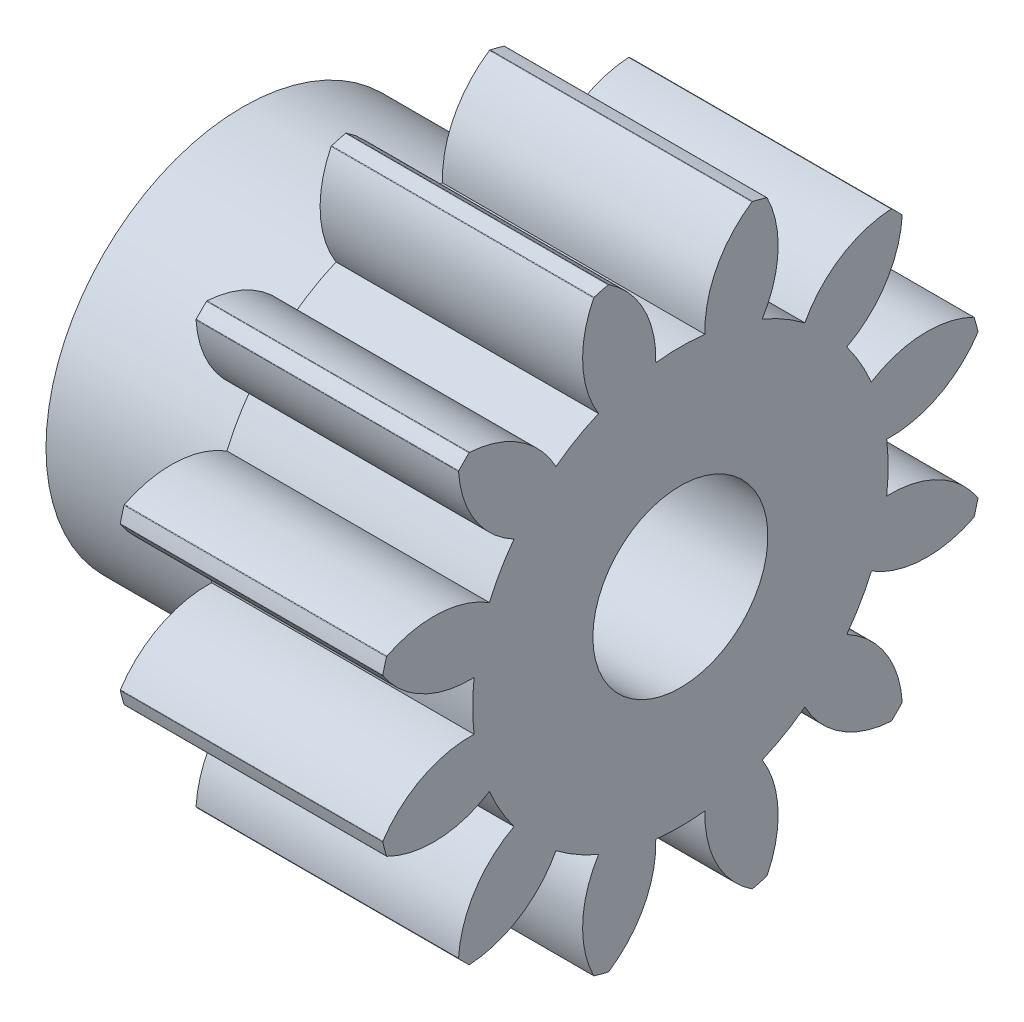
SolidWorks part; units mm, degrees
material "1.7035 (41Cr4)"
ref_plane "Plane1" through (0, 0, 0) normal (0, 0, 1) x (1, 0, 0)
ref_plane "Plane2" through (0, 0, 0) normal (0, 1, 0) x (1, 0, 0)
ref_plane "Plane3" through (0, 0, 0) normal (1, 0, 0) x (0, 0, -1)
sketch "HoldingSke" plane through (0, 0, 0) normal (0, 1, 0) x (1, 0, 0)
  line L0 (0, 0) -> (0.9781, -0.2079)
  line L1 (-15, 0) -> (100, 0) construction
  line L2 (0, 0) -> (-2.1039, 2.3779)
  line L3 (0, 0) -> (-11.863, 4.5341)
  line L4 (0, 0) -> (8.4473, 1.7955)
  line L5 (0, 0) -> (-46.8476, -17.4728)
  line L6 (0, 0) -> (-4.9738, -3.3558)
  line L7 (-2.1039, 2.3779) -> (8.6586, 51.2059)
  line L8 (-76.2, 54.61) -> (-75.5, 54.61)
  line L9 (-71.009, 38.7566) -> (-53.1078, 45.2721)
  line L10 (-76.2, 71.12) -> (104.1128, 71.12)
  line L11 (0, 0) -> (-6, 0)
  line L12 (-76.2, 101.6) -> (-76.162, 101.6)
  line L13 (24.9733, 27.94) -> (52.9518, 28.4284)
  line L14 (24.9733, 27.94) -> (24.9743, 27.94)
  line L15 (24.9733, 27.94) -> (100.4006, 29.5858)
  line L16 (-63.627, -1) -> (-12.827, -1)
  circle A0 centre (0, 0) radius 2
  circle A1 centre (0, 0) radius 4.749
  circle A2 centre (0, 0) radius 37.5
  circle A3 centre (0, 0) radius 2
  dimension "Num_teeth" = 12
  dimension "Pitch_radius" = 180.3128
  dimension "Width" = 6
  dimension "Thickness" = 6
sketch "BasProSke" plane through (0, 0, 0) normal (0, 1, 0) x (1, 0, 0)
  line L0 (-10, 0) -> (60, 0) construction
  line L1 (0, 0) -> (0, 7)
  line L2 (0, 0) -> (6, 0)
  line L3 (6, 0) -> (6, 7)
  line L4 (6, 7) -> (0, 7)
  dimension "Thickness" = 6
  dimension "Diameter" = 14
revolve "Base-Revolve" add sketch "BasProSke" angle 360 about L0
sketch "TooCutSke" plane through (0, 0, 0) normal (1, 0, 0) x (0, 0, -1)
  line L1 (0, 0) -> (0, 107) construction
  line L2 (0, 0) -> (-0.8496, 5.9395) construction
  line L3 (0, 0) -> (-3.0836, 11.5081) construction
  line L4 (-0.8496, 5.9395) -> (-1.5418, 5.7541) construction
  arc A0 (0.5622, 4.7156) -> (-0.5622, 4.7156) centre (0, 0) ccw
  arc A1 (1.6729, 6.8233) -> (-1.6729, 6.8233) centre (0, 0) ccw
  circle A2 centre (0, 0) radius 6 construction
  circle A3 centre (0, 0) radius 5.6382 construction
  arc A4 (-0.5622, 4.7156) -> (-1.6729, 6.8233) centre (-2.9608, 4.7982) ccw
  arc A5 (1.6729, 6.8233) -> (0.5622, 4.7156) centre (2.9608, 4.7982) ccw
extrude "ToothCut" cut sketch "TooCutSke" along normal through all
fillet "Breaks" radius 0.02 2 edges at (3, 6.8043, -1.6435) (3, 6.8043, 1.6435) tangent propagation no
fillet "RootFillets" [suppressed] radius 0.251
pattern_circular "TeethCuts" count 12 over 360 about axis through (-10, 0, 0) along (1, 0, 0) of "ToothCut", "Breaks", "RootFillets"
sketch "HubNeaOneSke" plane through (0, 0, 0) normal (-1, 0, 0) x (0, 0, 1)
  circle A0 centre (0, 0) radius 4.749
  dimension "Diameter" = 9.498
extrude "HubNearOne" [suppressed] add sketch "HubNeaOneSke" along normal blind 44.0001
sketch "HubNeaBotSke" plane through (0, 0, 0) normal (-1, 0, 0) x (0, 0, 1)
  circle A0 centre (0, 0) radius 4.749
  dimension "Diameter" = 9.498
extrude "HubNearBoth" [suppressed] add sketch "HubNeaBotSke" along normal blind 22
ref_plane "FarPln" through (6, 0, 0) normal (1, 0, 0) x (0, 0, -1)
sketch "HubFarSke" plane through (6, 0, 0) normal (1, 0, 0) x (0, 0, -1)
  circle A0 centre (0, 0) radius 4.749
  dimension "Diameter" = 9.498
extrude "HubFar" [suppressed] add sketch "HubFarSke" along normal blind 22
sketch "BorSke" plane through (0, 0, 0) normal (1, 0, 0) x (0, 0, -1)
  circle A0 centre (0, 0) radius 2
  dimension "Diameter" = 4
extrude "Bore" cut sketch "BorSke" along normal mid plane 100.0001
sketch "KeySke" plane through (0, 0, 0) normal (1, 0, 0) x (0, 0, -1)
  line L0 (-0.8, 0) -> (-0.8, 2.7)
  line L1 (-0.8, 2.7) -> (0.8, 2.7)
  line L2 (0.8, 2.7) -> (0.8, 0)
  line L3 (0, 0) -> (0, 34) construction
  line L4 (-0.8, 0) -> (0.8, 0)
  dimension "Width" = 1.6
extrude "Keyway" [suppressed] cut sketch "KeySke" along normal mid plane 100.0001
pattern_circular "Keyway2" [suppressed] count 2 every 90 about axis through (-10, 0, 0) along (1, 0, 0) reverse direction yes
ref_plane "Плоскость1" through (-4, 0, 0) normal (-1, 0, 0) x (0, 0, 1)
sketch "Эскиз3" plane through (-4, 0, 0) normal (-1, 0, 0) x (0, 0, 1)
  line L0 (0, 0) -> (-0.9356, 2.3183) construction
  line L1 (-0.7859, 1.9474) -> (-0.723, 2.3932)
  line L2 (-0.7859, 1.9474) -> (-1.1405, 2.2247)
  line L3 (-0.1456, 2.0949) -> (0.0519, 2.4995)
  line L4 (-0.1456, 2.0949) -> (-0.3972, 2.4682)
  line L5 (0, 0) -> (-0.1734, 2.494) construction
  line L6 (0.5089, 2.0374) -> (0.8217, 2.3611)
  line L7 (0.5089, 2.0374) -> (0.385, 2.4702)
  line L8 (0, 0) -> (0.6058, 2.4255) construction
  line L9 (1.1136, 1.7804) -> (1.5111, 1.9916)
  line L10 (1.1136, 1.7804) -> (1.1295, 2.2303)
  line L11 (0, 0) -> (1.3257, 2.1196) construction
  line L12 (1.6093, 1.3492) -> (2.0526, 1.4272)
  line L13 (1.6093, 1.3492) -> (1.7634, 1.7721)
  line L14 (0, 0) -> (1.9158, 1.6062) construction
  line L15 (1.9474, 0.7859) -> (2.3932, 0.723)
  line L16 (1.9474, 0.7859) -> (2.2247, 1.1405)
  line L17 (0, 0) -> (2.3183, 0.9356) construction
  line L18 (2.0949, 0.1456) -> (2.4995, -0.0519)
  line L19 (2.0949, 0.1456) -> (2.4682, 0.3972)
  line L20 (0, 0) -> (2.494, 0.1734) construction
  line L21 (2.0374, -0.5089) -> (2.3611, -0.8217)
  line L22 (2.0374, -0.5089) -> (2.4702, -0.385)
  line L23 (0, 0) -> (2.4255, -0.6058) construction
  line L24 (1.7804, -1.1136) -> (1.9916, -1.5111)
  line L25 (1.7804, -1.1136) -> (2.2303, -1.1295)
  line L26 (0, 0) -> (2.1196, -1.3257) construction
  line L27 (1.3492, -1.6093) -> (1.4272, -2.0526)
  line L28 (1.3492, -1.6093) -> (1.7721, -1.7634)
  line L29 (0, 0) -> (1.6062, -1.9158) construction
  line L30 (0.7859, -1.9474) -> (0.723, -2.3932)
  line L31 (0.7859, -1.9474) -> (1.1405, -2.2247)
  line L32 (0, 0) -> (0.9356, -2.3183) construction
  line L33 (0.1456, -2.0949) -> (-0.0519, -2.4995)
  line L34 (0.1456, -2.0949) -> (0.3972, -2.4682)
  line L35 (0, 0) -> (0.1734, -2.494) construction
  line L36 (-0.5089, -2.0374) -> (-0.8217, -2.3611)
  line L37 (-0.5089, -2.0374) -> (-0.385, -2.4702)
  line L38 (0, 0) -> (-0.6058, -2.4255) construction
  line L39 (-1.1136, -1.7804) -> (-1.5111, -1.9916)
  line L40 (-1.1136, -1.7804) -> (-1.1295, -2.2303)
  line L41 (0, 0) -> (-1.3257, -2.1196) construction
  line L42 (-1.6093, -1.3492) -> (-2.0526, -1.4272)
  line L43 (-1.6093, -1.3492) -> (-1.7634, -1.7721)
  line L44 (0, 0) -> (-1.9158, -1.6062) construction
  line L45 (-1.9474, -0.7859) -> (-2.3932, -0.723)
  line L46 (-1.9474, -0.7859) -> (-2.2247, -1.1405)
  line L47 (0, 0) -> (-2.3183, -0.9356) construction
  line L48 (-2.0949, -0.1456) -> (-2.4995, 0.0519)
  line L49 (-2.0949, -0.1456) -> (-2.4682, -0.3972)
  line L50 (0, 0) -> (-2.494, -0.1734) construction
  line L51 (-2.0374, 0.5089) -> (-2.3611, 0.8217)
  line L52 (-2.0374, 0.5089) -> (-2.4702, 0.385)
  line L53 (0, 0) -> (-2.4255, 0.6058) construction
  line L54 (-1.7804, 1.1136) -> (-1.9916, 1.5111)
  line L55 (-1.7804, 1.1136) -> (-2.2303, 1.1295)
  line L56 (0, 0) -> (-2.1196, 1.3257) construction
  line L57 (-1.3492, 1.6093) -> (-1.4272, 2.0526)
  line L58 (-1.3492, 1.6093) -> (-1.7721, 1.7634)
  line L59 (0, 0) -> (-1.6062, 1.9158) construction
  circle A0 centre (0, 0) radius 2.5
  circle A1 centre (0, 0) radius 2.1
  circle A2 centre (0, 0) radius 4.5
  circle A3 centre (0, 0) radius 2.2
  point P87 (0, 0)
  dimension "D1" = 5
  dimension "D2" = 4.2
  dimension "D4" = 9
  dimension "D6" = 4.4
  dimension "D3" = 30
  dimension "D5" = 20
extrude "Бобышка-Вытянуть2" add sketch "Эскиз3" against normal blind 4 separate body contours L1 A0 L2 | L3 A0 L4 | L6 A0 L7 | L9 A0 L10 | L12 A0 L13 | L15 A0 L16 | L18 A0 L19 | L57 A0 L58 | L54 A0 L55 | L51 A0 L52 | L48 A0 L49 | L45 A0 L46 | L42 A0 L43 | L39 A0 L40 | L36 A0 L37 | L21 A0 L22 | L24 A0 L25 | L27 A0 L28 | L30 A0 L31 | L33 A0 L34 | A2 A0 region at (-4, 2.205, -0.8898) region at (-4, 2.372, -0.1649) region at (-4, 1.8221, -1.5276) region at (-4, 2.3069, 0.5762) region at (-4, 1.2609, -2.0159) region at (-4, 2.0159, 1.2609) region at (-4, 0.5762, -2.3069) region at (-4, 1.5276, 1.8221) region at (-4, -0.1649, -2.372) region at (-4, 0.8898, 2.205) region at (-4, -0.8898, -2.205) region at (-4, 0.1649, 2.372) region at (-4, -1.5276, -1.8221) region at (-4, -2.0159, -1.2609) region at (-4, -0.5762, 2.3069) region at (-4, -2.3069, -0.5762) region at (-4, -1.2609, 2.0159) region at (-4, -2.372, 0.1649) region at (-4, -1.8221, 1.5276) region at (-4, -2.205, 0.8898) region at (-4, 0, -4.3727)
equation "' \"Module@HoldingSke\" = 6.35"
equation "' \"Num_teeth@HoldingSke\" = 12"
equation "' \"Ap@HoldingSke\" =  20"
equation "' \"Ap@HoldingSke\" = 20"
equation "' \"Width@HoldingSke\" = 0.5 * 25.4"
equation "' \"Hub_dia@HoldingSke\"= 1 * 25.4"
equation "' \"Hub_dia@HoldingSke\" = 1 * 25.4"
equation "' \"Overall_len@HoldingSke\" = 1.0 * 25.4"
equation "' \"Bore@HoldingSke\" = 0.75 * 25.4"
equation "' \"T_dim@HoldingSke\" = 0.1 * 25.4"
equation "' \"Width@KeySke\" = 0.25 * 25.4"
equation "' \"Show_teeth@HoldingSke\" = 13"
equation "' \"Backlash@HoldingSke\" = 0.009 * 25.4"
equation "' \"Addendum_fac@HoldingSke\" = 1.0"
equation "' \"Dedendum_fac@HoldingSke\" = 1.25"
equation "' \"Dedendum_add@HoldingSke\" = 0.00005 * 25.4"
equation "' \"Clearance_fac@HoldingSke\" = 0.25"
equation "\"Pitch@HoldingSke\" = 1 / \"Module@HoldingSke\""
equation "\"Overcut_dia@TooCutSke\" = (\"Num_teeth@HoldingSke\" + 2 * \"Addendum_fac@HoldingSke\") / \"Pitch@HoldingSke\" + 0.002 * 25.4"
equation "\"Pitch_dia@TooCutSke\" = \"Num_teeth@HoldingSke\" / \"Pitch@HoldingSke\""
equation "\"Base_dia@TooCutSke\" = \"Num_teeth@HoldingSke\" / \"Pitch@HoldingSke\" * cos((\"Ap@HoldingSke\"  * 3.14159265 / 180))"
equation "\"Root_dia@TooCutSke\" = (\"Num_teeth@HoldingSke\" + 2) / \"Pitch@HoldingSke\" - 2 * (\"Addendum_fac@HoldingSke\" + \"Dedendum_fac@HoldingSke\") / \"Pitch@HoldingSke\" - \"Dedendum_add@HoldingSke\" * 2"
equation "\"Half_ang@TooCutSke\" = 180 / \"Num_teeth@HoldingSke\""
equation "\"Half_CT@TooCutSke\" = \"Num_teeth@HoldingSke\" / \"Pitch@HoldingSke\" * sin((3.14159265 / 2 / \"Num_teeth@HoldingSke\")) / 2 - 7 * \"Backlash@HoldingSke\" / 4"
equation "\"Flank_rad@TooCutSke\" = \"Num_teeth@HoldingSke\" / \"Pitch@HoldingSke\" / 5"
equation "\"Radius@RootFillets\" = \"Clearance_fac@HoldingSke\" / \"Pitch@HoldingSke\" + \"Dedendum_add@HoldingSke\""
equation "\"Break_rad@Breaks\" = 0.02 / \"Pitch@HoldingSke\""
equation "\"Thickness@HoldingSke\" = \"Width@HoldingSke\""
equation "\"OAL@HoldingSke\" = \"Thickness@HoldingSke\""
equation "\"MHD@HoldingSke\" = (\"Num_teeth@HoldingSke\" + 2) / \"Pitch@HoldingSke\" - 2 * (\"Addendum_fac@HoldingSke\" + \"Dedendum_fac@HoldingSke\")  / \"Pitch@HoldingSke\" - \"Dedendum_add@HoldingSke\" * 2"
equation "\"MBD@HoldingSke\" = (\"Num_teeth@HoldingSke\" + 2) / \"Pitch@HoldingSke\" - 2 * (\"Addendum_fac@HoldingSke\" + \"Dedendum_fac@HoldingSke\")  / \"Pitch@HoldingSke\" - \"Dedendum_add@HoldingSke\" * 2 - 0.002 * 25.4"
equation "\"MHD@HoldingSke\" = ((sgn( \"MHD@HoldingSke\" - \"Hub_dia@HoldingSke\" )-1)*( \"MHD@HoldingSke\" - \"Hub_dia@HoldingSke\" ))/-2+ \"Hub_dia@HoldingSke\""
equation "\"MBD@HoldingSke\" = ((sgn( \"MBD@HoldingSke\" - \"Bore@HoldingSke\" )-1)*( \"MBD@HoldingSke\" - \"Bore@HoldingSke\" ))/-2+ \"Bore@HoldingSke\""
equation "\"OAL@HoldingSke\" = ((sgn( \"OAL@HoldingSke\" - \"Overall_len@HoldingSke\" )+1)*( \"OAL@HoldingSke\" - \"Overall_len@HoldingSke\" ))/2 + \"Overall_len@HoldingSke\" + 0.000002 * 25.4"
equation "\"Num_teeth@TeethCuts\" = int( \"Show_teeth@HoldingSke\" ) + 1"
equation "\"Num_teeth@TeethCuts\" = ((sgn( \"Num_teeth@TeethCuts\" - \"Num_teeth@HoldingSke\" )-1)*( \"Num_teeth@TeethCuts\" - \"Num_teeth@HoldingSke\" ))/-2+ \"Num_teeth@HoldingSke\""
equation "\"Num_teeth@TeethCuts\" = ((sgn( \"Num_teeth@TeethCuts\" - 2.0)+1)*( \"Num_teeth@TeethCuts\" - 2.0))/2 +2.0"
equation "\"Angle@TeethCuts\" = 360.0 / \"Num_teeth@HoldingSke\""
equation "\"Diameter@BasProSke\" = (\"Num_teeth@HoldingSke\" + 2 * \"Addendum_fac@HoldingSke\") / \"Pitch@HoldingSke\""
equation "\"Thickness@BasProSke\"  = \"Thickness@HoldingSke\""
equation "' \"Fillet_rad@BasProSke\" =  \"Thickness@HoldingSke\" * 0.05"
equation "' \"Fillet_rad@BasProSke\" = \"Thickness@HoldingSke\" * 0.05"
equation "\"MHD@HoldingSke\" = ((sgn( \"MHD@HoldingSke\" - \"Root_dia@TooCutSke\" )-1)*( \"MHD@HoldingSke\" - \"Root_dia@TooCutSke\" ))/-2+ \"Root_dia@TooCutSke\""
equation "\"Diameter@HubNeaOneSke\" = \"MHD@HoldingSke\""
equation "\"Length@HubNearOne\" = \"OAL@HoldingSke\" - \"Thickness@BasProSke\""
equation "\"Diameter@HubNeaBotSke\" = \"MHD@HoldingSke\""
equation "\"Length@HubNearBoth\" = ( \"OAL@HoldingSke\" - \"Thickness@BasProSke\" ) / 2.0"
equation "\"Thickness@FarPln\" = \"Thickness@BasProSke\""
equation "\"Diameter@HubFarSke\" = \"MHD@HoldingSke\""
equation "\"Length@HubFar\" = ( \"OAL@HoldingSke\" - \"Thickness@BasProSke\" ) / 2.0"
equation "\"Diameter@BorSke\" = \"MBD@HoldingSke\""
equation "\"D1@Bore\" = \"OAL@HoldingSke\" * 2.0"
equation "\"D1@Keyway\" = \"OAL@HoldingSke\" * 2.0"
equation "\"Offset@KeySke\" = \"T_dim@HoldingSke\" + \"MBD@HoldingSke\" / 2.0"
